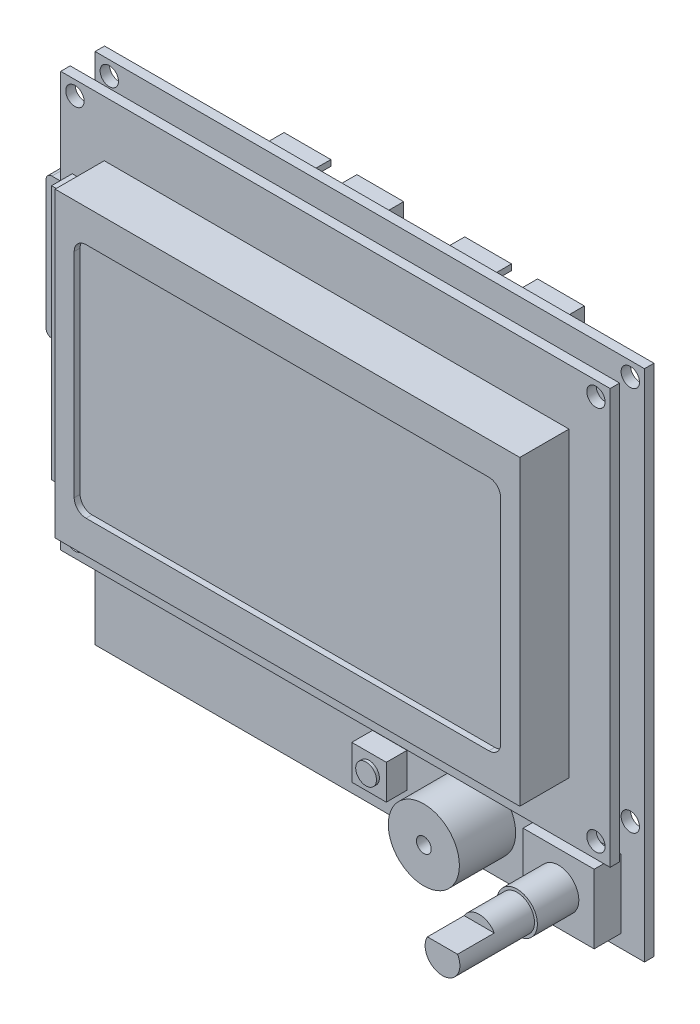
SolidWorks part; units mm, degrees
ref_plane "Front Plane" through (0, 0, 0) normal (0, 0, 1) x (1, 0, 0)
ref_plane "Top Plane" through (0, 0, 0) normal (0, 1, 0) x (1, 0, 0)
ref_plane "Right Plane" through (0, 0, 0) normal (1, 0, 0) x (0, 0, -1)
sketch "Sketch1" plane through (0, 0, 0) normal (0, 0, 1) x (1, 0, 0)
  line L1 (-46.375, -43.375) -> (46.375, -43.375)
  line L2 (-46.375, -43.375) -> (-46.375, 43.375)
  line L3 (-46.375, 43.375) -> (46.375, 43.375)
  line L4 (46.375, -43.375) -> (46.375, 43.375)
  line L6 (-43.975, 40.975) -> (43.975, 40.975) construction
  line L7 (-43.975, 40.975) -> (-43.975, -24.025) construction
  line L8 (-43.975, -24.025) -> (43.975, -24.025) construction
  line L9 (43.975, 40.975) -> (43.975, -24.025) construction
  circle A0 centre (-43.975, 40.975) radius 1.55
  circle A1 centre (43.975, 40.975) radius 1.55
  circle A2 centre (43.975, -24.025) radius 1.55
  circle A3 centre (-43.975, -24.025) radius 1.55
  point P5 (0, 43.375)
  point P6 (-46.375, 0)
  dimension "D3" = 3.1
  dimension "D1" = 86.75
  dimension "D2" = 92.75
  dimension "D4" = 2.4
  dimension "D5" = 2.4
  dimension "D6" = 2.4
  dimension "D7" = 65
extrude "Boss-Extrude1 - First PCB" add sketch "Sketch1" along normal blind 1.6
sketch "Sketch2" plane through (0, 0, 1.6) normal (0, 0, 1) x (1, 0, 0)
  line L0 (-46.375, -43.375) -> (46.375, -43.375) construction
  line L1 (-46.375, -43.375) -> (-46.375, 43.375) construction
  circle A0 centre (18.625, -35.375) radius 6
  dimension "D1" = 12
  dimension "D2" = 8
  dimension "D3" = 65
extrude "Boss-Extrude2 - Speaker" add sketch "Sketch2" along normal blind 9.5
sketch "Sketch15" plane through (0, 0, 11.1) normal (0, 0, 1) x (1, 0, 0)
  circle A0 centre (18.625, -35.375) radius 1.25
  dimension "D1" = 2.5
extrude "Cut-Extrude1 - Speaker Hole" cut sketch "Sketch15" against normal blind 5
sketch "Sketch3" plane through (0, 0, 1.6) normal (0, 0, 1) x (-1, 0, 0)
  line L1 (-42.375, 41.2) -> (-30.375, 41.2)
  line L2 (-42.375, 41.2) -> (-42.375, 29.55)
  line L3 (-42.375, 29.55) -> (-30.375, 29.55)
  line L4 (-30.375, 41.2) -> (-30.375, 29.55)
  line L8 (-30.375, 35.375) -> (-18.625, 35.375) construction
  line L10 (-36.375, 41.2) -> (-36.375, 29.55) construction
  line L11 (-46.375, 43.375) -> (-46.375, -43.375) construction
  circle A1 centre (-18.625, 35.375) radius 6 construction
  point P19 (-13.8797, 31.7032)
  dimension "D1" = 11.65
  dimension "D2" = 12
  dimension "D3" = 10
extrude "Boss-Extrude3 - Rotary Switch" add sketch "Sketch3" along normal blind 4.5
sketch "Sketch4" plane through (0, 0, 1.6) normal (0, 0, 1) x (-1, 0, 0)
  line L0 (-3.375, 38.29) -> (-3.375, 32.46) construction
  line L1 (-6.29, 38.29) -> (-0.46, 38.29)
  line L2 (-6.29, 38.29) -> (-6.29, 32.46)
  line L3 (-6.29, 32.46) -> (-0.46, 32.46)
  line L4 (-0.46, 38.29) -> (-0.46, 32.46)
  line L5 (-6.29, 35.375) -> (-0.46, 35.375) construction
  line L6 (-6.29, 35.375) -> (-18.625, 35.375) construction
  line L15 (-46.375, 43.375) -> (-46.375, -43.375) construction
  point P8 (-3.375, 35.375)
  dimension "D1" = 5.83
  dimension "D2" = 5.83
  dimension "D3" = 43
extrude "Boss-Extrude4 - Reset Switch" add sketch "Sketch4" along normal blind 3.5
sketch "Sketch5" plane through (0, 0, 5.1) normal (0, 0, 1) x (-1, 0, 0)
  line L1 (-6.29, 38.29) -> (-0.46, 32.46) construction
  line L2 (-0.46, 38.29) -> (-6.29, 32.46) construction
  circle A0 centre (-3.375, 35.375) radius 1.75
  dimension "D1" = 3.5
extrude "Boss-Extrude5 - Reset Button" add sketch "Sketch5" along normal blind 0.5
sketch "Sketch16" plane through (0, 0, 6.1) normal (0, 0, 1) x (1, 0, 0)
  line L0 (30.375, -29.55) -> (30.375, -41.2) construction
  line L1 (42.375, -29.55) -> (30.375, -29.55) construction
  circle A0 centre (36.375, -35.375) radius 3.415
  point P4 (30.375, -35.375)
  point P7 (36.375, -29.55)
  dimension "D1" = 6.83
extrude "Boss-Extrude6 - Rotary Switch" add sketch "Sketch16" along normal blind 7
sketch "Sketch17" plane through (0, 0, 13.1) normal (0, 0, 1) x (1, 0, 0)
  circle A0 centre (36.375, -35.375) radius 2.935
  dimension "D1" = 5.87
extrude "Boss-Extrude7 - Rotary Switch" add sketch "Sketch17" along normal blind 6.4
sketch "Sketch18" plane through (0, 0, 19.5) normal (0, 0, 1) x (1, 0, 0)
  line L0 (33.8318, -33.91) -> (38.9182, -33.91)
  arc A0 (33.8318, -33.91) -> (38.9182, -33.91) centre (36.375, -35.375) ccw
  circle A1 centre (36.375, -35.375) radius 2.935 construction
  point P6 (36.375, -38.31)
  dimension "D1" = 4.4
extrude "Boss-Extrude8 - Rotary Switch" add sketch "Sketch18" along normal offset from surface (6.2 mm away) 24.1 up to face at (36.375, -35.375, 1.6) offset beyond the face yes
sketch "Sketch9" plane through (0, 0, 0) normal (0, 0, -1) x (1, 0, 0)
  line L0 (-46.375, -43.375) -> (46.375, -43.375) construction
  line L1 (-46.125, 5.425) -> (-27.875, 5.425)
  line L2 (-46.125, 5.425) -> (-46.125, -20.975)
  line L3 (-46.125, -20.975) -> (-20.375, -20.975)
  line L4 (-20.375, 3.425) -> (-20.375, -20.975)
  line L6 (-20.375, 3.425) -> (-25.875, 3.425)
  line L7 (-25.875, 3.425) -> (-27.875, 5.425)
  line L8 (-46.375, -43.375) -> (-46.375, 43.375) construction
  dimension "D1" = 22.4
  dimension "D2" = 26.4
  dimension "D3" = 0.25
  dimension "D4" = 18.25
  dimension "D5" = 2
  dimension "D6" = 45
  dimension "D7" = 25.75
extrude "Boss-Extrude9 - SD Card Slot" add sketch "Sketch9" along normal blind 3
sketch "Sketch19" plane through (0, 0, 1.6) normal (0, 0, 1) x (1, 0, 0)
  line L0 (-46.375, 43.375) -> (-46.375, -43.375) construction
  line L1 (-33.375, -22.875) -> (16.625, -22.875)
  line L2 (-33.375, -22.875) -> (-33.375, -25.375)
  line L3 (-33.375, -25.375) -> (16.625, -25.375)
  line L4 (16.625, -22.875) -> (16.625, -25.375)
  line L5 (-46.375, -43.375) -> (46.375, -43.375) construction
  dimension "D1" = 2.5
  dimension "D2" = 50
  dimension "D3" = 13
  dimension "D4" = 18
extrude "Boss-Extrude10 - Connector" add sketch "Sketch19" along normal blind 4.2
sketch "Sketch11" plane through (0, -2, 5.8) normal (0, 0, -1) x (1, 0, 0)
  line L1 (46.375, 24.625) -> (-46.375, 24.625)
  line L2 (46.375, 24.625) -> (46.375, -45.375)
  line L3 (46.375, -45.375) -> (-46.375, -45.375)
  line L4 (-46.375, 24.625) -> (-46.375, -45.375)
  line L8 (46.375, 41.375) -> (46.375, -45.375) construction
  circle A0 centre (-43.975, -42.975) radius 1.55 construction
  circle A1 centre (-43.975, -42.975) radius 1.55
  circle A2 centre (-43.975, 22.025) radius 1.55 construction
  circle A3 centre (43.975, -42.975) radius 1.55 construction
  circle A4 centre (43.975, 22.025) radius 1.55 construction
  circle A5 centre (-43.975, 22.025) radius 1.55
  circle A6 centre (43.975, -42.975) radius 1.55
  circle A7 centre (43.975, 22.025) radius 1.55
  dimension "D2" = 70
extrude "Boss-Extrude11 - Upper PCB" add sketch "Sketch11" against normal blind 1.6
sketch "Sketch12" plane through (0, 0, 7.4) normal (0, 0, 1) x (-1, 0, 0)
  line L1 (-39.425, 17.025) -> (39.025, 17.025)
  line L2 (-39.425, 17.025) -> (-39.425, -33.975)
  line L3 (-39.425, -33.975) -> (39.025, -33.975)
  line L4 (39.025, 17.025) -> (39.025, -33.975)
  line L6 (46.375, -43.375) -> (-46.375, -43.375) construction
  line L7 (46.375, 26.625) -> (46.375, -43.375) construction
  dimension "D1" = 51
  dimension "D2" = 78.45
  dimension "D3" = 9.4
  dimension "D4" = 7.35
extrude "Boss-Extrude12 - LCD" add sketch "Sketch12" along normal blind 8.3
sketch "Sketch24" plane through (0, 0, 7.4) normal (0, 0, 1) x (1, 0, 0)
  line L0 (-39.025, 33.975) -> (-39.025, -17.025) construction
  line L1 (-39.025, 29.375) -> (-44.425, 29.375)
  line L2 (-39.025, 29.375) -> (-39.025, -13.625)
  line L3 (-39.025, -13.625) -> (-44.425, -13.625)
  line L4 (-44.425, 29.375) -> (-44.425, -13.625)
  line L5 (39.425, 33.975) -> (-39.025, 33.975) construction
  dimension "D1" = 5.4
  dimension "D2" = 43
  dimension "D3" = 4.6
extrude "Boss-Extrude13 - LCD Bumpout" add sketch "Sketch24" along normal blind 3.5
sketch "Sketch13" plane through (0, 0, 15.7) normal (0, 0, 1) x (-1, 0, 0)
  line L0 (-0.2, 17.025) -> (-0.2, -33.975) construction
  line L2 (-39.425, -33.975) -> (39.025, -33.975) construction
  line L3 (-39.425, -8.475) -> (39.025, -8.475) construction
  line L4 (-39.425, 17.025) -> (-39.425, -33.975) construction
  line L5 (39.025, -33.975) -> (39.025, 17.025) construction
  line L6 (-0.2, 11.525) -> (-0.2, -28.475) construction
  line L7 (-34.2, 11.525) -> (33.8, 11.525)
  line L8 (-36.2, 9.525) -> (-36.2, -26.475)
  line L9 (-34.2, -28.475) -> (33.8, -28.475)
  line L10 (35.8, 9.525) -> (35.8, -26.475)
  line L11 (-39.425, 17.025) -> (39.025, 17.025) construction
  arc A8 (33.8, 11.525) -> (35.8, 9.525) centre (33.8, 9.525) cw
  arc A9 (-36.2, -26.475) -> (-34.2, -28.475) centre (-34.2, -26.475) ccw
  arc A10 (-34.2, 11.525) -> (-36.2, 9.525) centre (-34.2, 9.525) ccw
  arc A11 (33.8, -28.475) -> (35.8, -26.475) centre (33.8, -26.475) ccw
  point P18 (-0.2, -8.475)
  point P19 (-0.2, -8.475)
  point P62 (-36.2, -28.475)
  point P65 (-36.2, 11.525)
  dimension "D8" = 2
  dimension "D1" = 40
  dimension "D2" = 72
extrude "Cut-Extrude2 - Screen Recess" cut sketch "Sketch13" against normal blind 1 contours L10 L7 L8 L9 region at (0.2, 8.475, 15.7)
sketch "Sketch21" plane through (0, 0, 0) normal (0, 0, -1) x (-1, 0, 0)
  line L0 (-46.375, -43.375) -> (-46.375, 43.375) construction
  line L1 (-25.625, 36.875) -> (-5.425, 36.875)
  line L2 (-25.625, 36.875) -> (-25.625, 28.025)
  line L3 (-25.625, 28.025) -> (-5.425, 28.025)
  line L4 (-5.425, 36.875) -> (-5.425, 28.025)
  line L5 (4.875, 36.875) -> (25.075, 36.875)
  line L6 (4.875, 36.875) -> (4.875, 28.025)
  line L7 (4.875, 28.025) -> (25.075, 28.025)
  line L8 (25.075, 36.875) -> (25.075, 28.025)
  line L9 (-46.375, 43.375) -> (46.375, 43.375) construction
  line L10 (-24.625, 35.875) -> (-6.425, 35.875)
  line L11 (-6.425, 35.875) -> (-6.425, 29.025)
  line L12 (-24.625, 29.025) -> (-6.425, 29.025)
  line L13 (-24.625, 35.875) -> (-24.625, 29.025)
  line L14 (5.875, 35.875) -> (24.075, 35.875)
  line L15 (24.075, 35.875) -> (24.075, 29.025)
  line L16 (5.875, 29.025) -> (24.075, 29.025)
  line L17 (5.875, 35.875) -> (5.875, 29.025)
  dimension "D1" = 20.2
  dimension "D2" = 10.3
  dimension "D3" = 8.85
  dimension "D4" = 20.75
  dimension "D5" = 6.5
  dimension "D6" = 1
  dimension "D7" = 1
extrude "Boss-Extrude14 - Connectors" add sketch "Sketch21" along normal blind 9
sketch "Sketch22" plane through (0, 0, 0) normal (0, 0, -1) x (-1, 0, 0)
  line L4 (-24.625, 35.875) -> (-24.625, 29.025)
  line L5 (-24.625, 29.025) -> (-6.425, 29.025)
  line L6 (-6.425, 29.025) -> (-6.425, 35.875)
  line L7 (-6.425, 35.875) -> (-24.625, 35.875)
  line L8 (-24.625, 35.875) -> (-24.625, 29.025)
  line L9 (-24.625, 29.025) -> (-6.425, 29.025)
  line L10 (-6.425, 29.025) -> (-6.425, 35.875)
  line L11 (-6.425, 35.875) -> (-24.625, 35.875)
  line L12 (5.875, 35.875) -> (5.875, 29.025)
  line L13 (5.875, 29.025) -> (24.075, 29.025)
  line L14 (24.075, 29.025) -> (24.075, 35.875)
  line L15 (24.075, 35.875) -> (5.875, 35.875)
  line L16 (5.875, 35.875) -> (5.875, 29.025)
  line L17 (5.875, 29.025) -> (24.075, 29.025)
  line L18 (24.075, 29.025) -> (24.075, 35.875)
  line L19 (24.075, 35.875) -> (5.875, 35.875)
  dimension "D1" = 0
  dimension "D2" = 0
extrude "Boss-Extrude15 - Connector Recess" add sketch "Sketch22" along normal blind 2.55
sketch "Sketch23" plane through (0, 0, -9) normal (0, 0, -1) x (-1, 0, 0)
  line L0 (-5.425, 36.875) -> (-25.625, 36.875) construction
  line L1 (-17.725, 36.875) -> (-13.325, 36.875)
  line L2 (-17.725, 36.875) -> (-17.725, 35.875)
  line L3 (-17.725, 35.875) -> (-13.325, 35.875)
  line L4 (-13.325, 36.875) -> (-13.325, 35.875)
  line L5 (-6.425, 35.875) -> (-24.625, 35.875) construction
  line L6 (25.075, 36.875) -> (4.875, 36.875) construction
  line L7 (12.775, 36.875) -> (17.175, 36.875)
  line L8 (12.775, 36.875) -> (12.775, 35.875)
  line L9 (12.775, 35.875) -> (17.175, 35.875)
  line L10 (17.175, 36.875) -> (17.175, 35.875)
  line L11 (24.075, 35.875) -> (5.875, 35.875) construction
  line L12 (14.975, 29.025) -> (14.975, 36.875) construction
  line L13 (5.875, 29.025) -> (24.075, 29.025) construction
  line L14 (-15.525, 29.025) -> (-15.525, 36.875) construction
  line L15 (-24.625, 29.025) -> (-6.425, 29.025) construction
  point P20 (14.975, 36.875)
  point P25 (-15.525, 36.875)
  dimension "D1" = 4.4
extrude "Cut-Extrude3 - Connector Notch" cut sketch "Sketch23" against normal up to surface (6.45 mm away) up to face at (15.525, 32.45, -2.55)
sketch "Sketch20" plane through (-46.125, 0, 0) normal (-1, 0, 0) x (0, 0, 1)
  line L0 (1.6, 43.375) -> (1.6, -43.375) construction
  line L1 (-2.423, 19.65) -> (-0.27, 19.65)
  line L2 (-2.423, 19.65) -> (-2.423, -4.1)
  line L3 (-2.423, -4.1) -> (-0.27, -4.1)
  line L4 (-0.27, 19.65) -> (-0.27, -4.1)
  line L5 (-3, 7.775) -> (-2.423, 7.775) construction
  line L6 (-3, -5.425) -> (-3, 20.975) construction
  dimension "D1" = 23.75
  dimension "D2" = 2.153
  dimension "D3" = 1.87
extrude "Boss-Extrude16 - SD Card" add sketch "Sketch20" along normal blind 10.4
fillet "Fillet1 - SD Card" radius 1 2 edges at (-56.525, -4.1, -1.3465) (-56.525, 19.65, -1.3465)
